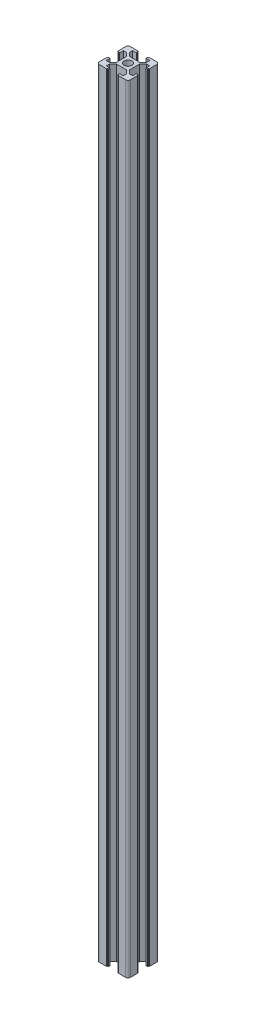
SolidWorks part; units mm, degrees
ref_plane "Front Plane" through (0, 0, 0) normal (0, 0, 1) x (1, 0, 0)
ref_plane "Top Plane" through (0, 0, 0) normal (0, 1, 0) x (1, 0, 0)
ref_plane "Right Plane" through (0, 0, 0) normal (1, 0, 0) x (0, 0, -1)
sketch "Sketch1" plane through (0, 0, 0) normal (0, 1, 0) x (1, 0, 0)
  line L0 (-8.5, 8.5) -> (8.5, 8.5)
  line L1 (-8.5, -10) -> (8.5, -10)
  line L2 (-10, -8.5) -> (-10, 8.5)
  line L3 (-8.5, 10) -> (8.5, 10)
  line L4 (10, -8.5) -> (10, 8.5)
  line L5 (-10, -10) -> (10, 10) construction
  line L6 (-10, 10) -> (10, -10) construction
  line L7 (8.5, -8.5) -> (8.5, 8.5)
  line L8 (-8.5, -8.5) -> (8.5, -8.5)
  line L9 (-8.5, -8.5) -> (-8.5, 8.5)
  line L10 (-10.4243, 9.5757) -> (9.5757, -10.4243)
  line L11 (-9.5757, -10.4243) -> (10.4243, 9.5757)
  line L12 (-9.5757, 10.4243) -> (10.4243, -9.5757)
  line L13 (-10.4243, -9.5757) -> (9.5757, 10.4243)
  line L14 (-9.5, -8.5) -> (-9.5, 8.5)
  line L15 (-10, -5.5) -> (10, -5.5)
  line L16 (-10, -5.5) -> (-10, 5.5)
  line L17 (-10, 5.5) -> (10, 5.5)
  line L18 (10, -5.5) -> (10, 5.5)
  line L19 (-10, -5.5) -> (10, 5.5) construction
  line L20 (-10, 5.5) -> (10, -5.5) construction
  line L21 (5.5, -10) -> (-5.5, -10)
  line L22 (5.5, -10) -> (5.5, 10)
  line L23 (5.5, 10) -> (-5.5, 10)
  line L24 (-5.5, -10) -> (-5.5, 10)
  line L25 (5.5, -10) -> (-5.5, 10) construction
  line L26 (5.5, 10) -> (-5.5, -10) construction
  line L27 (10, -3.1) -> (-10, -3.1)
  line L28 (10, -3.1) -> (10, 3.1)
  line L29 (10, 3.1) -> (-10, 3.1)
  line L30 (-10, -3.1) -> (-10, 3.1)
  line L31 (10, -3.1) -> (-10, 3.1) construction
  line L32 (10, 3.1) -> (-10, -3.1) construction
  line L33 (10, -3.6) -> (-10, -3.6)
  line L34 (10, -3.6) -> (10, 3.6)
  line L35 (10, 3.6) -> (-10, 3.6)
  line L36 (-10, -3.6) -> (-10, 3.6)
  line L37 (10, -3.6) -> (-10, 3.6) construction
  line L38 (10, 3.6) -> (-10, -3.6) construction
  line L39 (-8.5, 9.5) -> (8.5, 9.5)
  line L40 (9.5, -8.5) -> (9.5, 8.5)
  line L41 (-8.5, -9.5) -> (8.5, -9.5)
  arc A0 (-8.5, 10) -> (-10, 8.5) centre (-8.5, 8.5) ccw
  arc A1 (10, 8.5) -> (8.5, 10) centre (8.5, 8.5) ccw
  arc A2 (8.5, -10) -> (10, -8.5) centre (8.5, -8.5) ccw
  arc A3 (-10, -8.5) -> (-8.5, -10) centre (-8.5, -8.5) ccw
  arc A4 (8.5, 8.5) -> (8.5, 8.5) centre (8.5, 8.5) ccw
  arc A5 (8.5, -8.5) -> (8.5, -8.5) centre (8.5, -8.5) ccw
  arc A6 (-8.5, -8.5) -> (-8.5, -8.5) centre (-8.5, -8.5) ccw
  arc A7 (-8.5, 8.5) -> (-8.5, 8.5) centre (-8.5, 8.5) ccw
  circle A8 centre (0, 0) radius 2.5
  arc A9 (-8.5, 9.5) -> (-9.5, 8.5) centre (-8.5, 8.5) ccw
  arc A10 (9.5, 8.5) -> (8.5, 9.5) centre (8.5, 8.5) ccw
  arc A11 (8.5, -9.5) -> (9.5, -8.5) centre (8.5, -8.5) ccw
  arc A12 (-9.5, -8.5) -> (-8.5, -9.5) centre (-8.5, -8.5) ccw
  point P0 (0, 0)
  point P38 (0, 0)
  point P43 (0, 0)
  dimension "D3" = 1.5
  dimension "D4" = 1.5
  dimension "D5" = 1.5
  dimension "D6" = 1.5
  dimension "D12" = 5
  dimension "D1" = 20
  dimension "D2" = 20
  dimension "D10" = 11
  dimension "D11" = 11
  dimension "D13" = 6.2
  dimension "D14" = 7.2
  dimension "D7" = 1.5
  dimension "D8" = 0.6
  dimension "D9" = 0.6
  dimension "D15" = 0.5
sketch "Sketch2" plane through (0, 0, 0) normal (0, 1, 0) x (1, 0, 0)
  line L0 (-10, -8.5) -> (-10, 8.5) construction
  line L1 (-8.5, 10) -> (8.5, 10) construction
  line L2 (10, -8.5) -> (10, 8.5) construction
  line L3 (-8.5, -10) -> (8.5, -10) construction
  line L4 (-10, -8.5) -> (-10, 8.5)
  line L5 (-8.5, 10) -> (8.5, 10)
  line L6 (10, -8.5) -> (10, 8.5)
  line L7 (-8.5, -10) -> (8.5, -10)
  arc A0 (-8.5, 10) -> (-10, 8.5) centre (-8.5, 8.5) ccw construction
  arc A1 (10, 8.5) -> (8.5, 10) centre (8.5, 8.5) ccw construction
  arc A2 (8.5, -10) -> (10, -8.5) centre (8.5, -8.5) ccw construction
  arc A3 (-10, -8.5) -> (-8.5, -10) centre (-8.5, -8.5) ccw construction
  arc A4 (-8.5, 10) -> (-10, 8.5) centre (-8.5, 8.5) ccw
  arc A5 (10, 8.5) -> (8.5, 10) centre (8.5, 8.5) ccw
  arc A6 (8.5, -10) -> (10, -8.5) centre (8.5, -8.5) ccw
  arc A7 (-10, -8.5) -> (-8.5, -10) centre (-8.5, -8.5) ccw
extrude "Boss-Extrude1" add sketch "Sketch2" along normal blind 500
sketch "Sketch3" plane through (0, 500, 0) normal (0, 1, 0) x (1, 0, 0)
  line L3 (4.2, -4.2) -> (-4.2, -4.2)
  line L4 (4.2, -4.2) -> (4.2, 4.2)
  line L5 (4.2, 4.2) -> (-4.2, 4.2)
  line L6 (-4.2, -3.3515) -> (-4.2, 3.3515)
  line L7 (4.2, -4.2) -> (-4.2, 4.2) construction
  line L8 (4.2, 4.2) -> (-4.2, -4.2) construction
  line L10 (-10.4243, 9.5757) -> (9.5757, -10.4243) construction
  line L11 (-9.5757, 10.4243) -> (10.4243, -9.5757) construction
  line L12 (-10.4243, 9.5757) -> (-4.2, 3.3515)
  line L13 (-9.5757, 10.4243) -> (10.4243, -9.5757)
  line L15 (-8.5, -8.5) -> (-8.5, 8.5) construction
  line L16 (-8.5, -8.5) -> (-8.5, -3.1)
  line L17 (-10, 5.5) -> (10, 5.5) construction
  line L19 (10, -3.1) -> (-10, -3.1) construction
  line L20 (10, -3.6) -> (-10, -3.6) construction
  line L22 (10, 3.6) -> (-10, 3.6) construction
  line L23 (-10, -8.5) -> (-10, 8.5) construction
  line L24 (-10.4243, -9.5757) -> (9.5757, 10.4243) construction
  line L25 (-8.5, 5.5) -> (10, 5.5)
  line L26 (-10, -5.5) -> (10, -5.5) construction
  line L27 (10, -3.1) -> (-4.2, -3.1)
  line L28 (10, -3.6) -> (-4.4485, -3.6)
  line L29 (-10, -5.5) -> (10, -5.5)
  line L30 (10, 3.6) -> (-4.4485, 3.6)
  line L31 (-10, -8.5) -> (-10, -3.8)
  line L32 (-10.4243, -9.5757) -> (-4.2, -3.3515)
  line L33 (-10, 3.8) -> (-10, 8.5)
  line L34 (10, 3.1) -> (-10, 3.1) construction
  line L35 (10, 3.1) -> (-4.2, 3.1)
  line L36 (-9.5, -3.6) -> (-9.8, -3.6)
  line L37 (-8.5, -3.1) -> (-9.3, -3.1)
  line L38 (-9.5, 3.3) -> (-9.5, 3.6)
  line L39 (-8.5, 3.1) -> (-8.5, 8.5)
  line L40 (-9.5, 3.6) -> (-9.8, 3.6)
  line L41 (-9.5, -3.6) -> (-9.5, -3.3)
  line L42 (4.6515, -5.5) -> (10, -5.5)
  line L43 (-8.5, 3.1) -> (-9.3, 3.1)
  line L44 (-9.5, -8.5) -> (-9.5, 8.5) construction
  line L45 (-10, -8.5) -> (-10, 8.5)
  arc A0 (-9.8, -3.6) -> (-10, -3.8) centre (-9.8, -3.8) ccw
  arc A1 (-9.3, -3.1) -> (-9.5, -3.3) centre (-9.3, -3.3) ccw
  arc A2 (-9.5, 3.3) -> (-9.3, 3.1) centre (-9.3, 3.3) ccw
  arc A3 (-10, 3.8) -> (-9.8, 3.6) centre (-9.8, 3.8) ccw
  circle A6 centre (0, 0) radius 2.5 construction
  circle A7 centre (0, 0) radius 2.5
  point P0 (0, 0)
  point P6 (-4.2, 3.3)
  point P12 (-4.2, -3.3769)
  point P40 (-4.2254, -3.3)
  point P46 (-4.1743, 3.3)
  point P55 (-9.5, 3.1)
  line M12 (-10, 8.5) -> (-10, -8.5)
  dimension "D2" = 0.2
  dimension "D3" = 0.2
  dimension "D4" = 0.2
  dimension "D5" = 0.2
  dimension "D7" = 4.3
extrude "Cut-Extrude1" cut sketch "Sketch3" against normal through all contours L39 L43 L38 L40 L36 L41 L37 L16 L29 L32 L6 L12 L25 M12 | L13 A7 | L13 A7 region at (-7.0241, 500, 0) region at (-0.5269, 500, 0.5269) region at (0.9842, 500, -0.9842)
ref_axis "Axis1" through (0, -20, 0) along (0, 1, 0)
pattern_circular "CirPattern1" count 4 over 360 about axis through (0, -20, 0) along (0, 1, 0) of "Cut-Extrude1"
sketch "Sketch4" plane through (0, 500, 0) normal (0, 1, 0) x (1, 0, 0)
sketch "Sketch5" plane through (0, 500, 0) normal (0, 1, 0) x (1, 0, 0)
  line L0 (-8.5, 3.1) -> (-9.3, 3.1) construction
  line L1 (-8.5, -3.1) -> (-9.3, -3.1) construction
  dimension "D1" = 6.2
